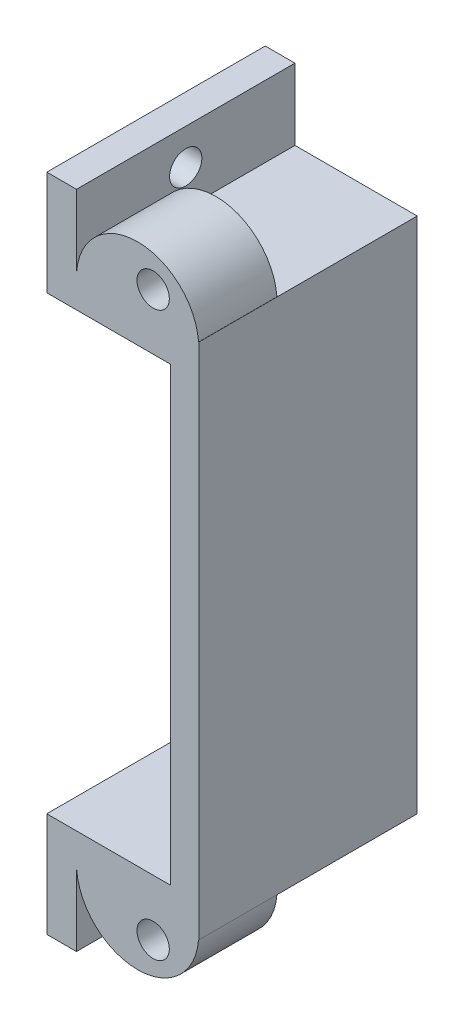
SolidWorks part; units mm, degrees
ref_plane "Front Plane" through (0, 0, 0) normal (0, 0, 1) x (1, 0, 0)
ref_plane "Top Plane" through (0, 0, 0) normal (0, 1, 0) x (1, 0, 0)
ref_plane "Right Plane" through (0, 0, 0) normal (1, 0, 0) x (0, 0, -1)
sketch "Sketch1" plane through (0, 0, 0) normal (0, 0, 1) x (1, 0, 0)
  line L0 (13, -24) -> (16, -24)
  line L1 (-13, -24) -> (13, -24) construction
  line L2 (-13, -24) -> (-13, 24) construction
  line L3 (-13, 24) -> (13, 24) construction
  line L4 (13, -24) -> (13, 24) construction
  line L5 (-13, -24) -> (13, 24) construction
  line L6 (-13, 24) -> (13, -24) construction
  line L7 (16, -24) -> (16, 27)
  line L8 (16, 27) -> (0, 27)
  line L10 (-13, 24) -> (13, 24)
  line L11 (13, 24) -> (13, -24)
  line L12 (0, 24) -> (0, 27) construction
  line L13 (3.1271, 24) -> (3.1271, 27)
  line L14 (9.5636, 24) -> (9.5636, 33.4364) construction
  line L15 (0, 27) -> (0, 34.5)
  line L16 (0, 24) -> (0, 27)
  line L17 (3.1271, 27) -> (3.1271, 34.5)
  line L18 (3.1271, 34.5) -> (0, 34.5)
  line L19 (0, -24) -> (0, -27)
  line L20 (0, -27) -> (16, -27)
  line L21 (16, -27) -> (16, -24)
  line L22 (13, -24) -> (0, -24)
  line L23 (3.1271, -24) -> (3.1271, -34.5)
  line L24 (3.1271, -34.5) -> (0, -34.5)
  line L25 (0, -34.5) -> (0, -27)
  line L26 (11.328, 27) -> (11.328, 24)
  arc A0 (3.1271, 27) -> (16, 27) centre (9.5636, 27) cw
  point P0 (0, 0)
  dimension "D1" = 26
  dimension "D2" = 48
  dimension "D3" = 3
  dimension "D4" = 3
  dimension "D5" = 7.5
  dimension "D6" = 3
  dimension "D7" = 10.5
extrude "Boss-Extrude1" add sketch "Sketch1" along normal blind 23 contours L13 L10 L11 L0 L7 L8 | L17 L18 L15 L8 | L16 L10 L13 L8 | L25 L24 L23 L20 | L23 L22 L19 L20 | L22 L23 L20 L21 L0 | A0 L8 | L26 L8 L13 L10 region at (14.4258, 2.2619, 0) region at (9.5636, -25.5, 0) region at (1.5636, -25.5, 0) region at (9.5636, 29.7317, 0) region at (7.2275, 25.5, 0) region at (1.5636, -30.75, 0) region at (1.5636, 25.5, 0) region at (1.5636, 30.75, 0)
sketch "Sketch2" plane through (3.1271, 0, 0) normal (1, 0, 0) x (0, 0, -1)
  line L0 (-23, 34.5) -> (0, 27) construction
  line L1 (0, 27) -> (0, 34.5) construction
  line L2 (0, 34.5) -> (-23, 27) construction
  line L3 (-14.75, 30.75) -> (-14.75, 34.5)
  line L4 (-23, 34.5) -> (0, 34.5) construction
  line L5 (-8.25, 30.75) -> (-8.25, 34.5)
  line L6 (-14.75, 34.5) -> (-8.25, 34.5)
  line L7 (-11.5, 27.5) -> (0, 27.5)
  line L8 (-11.5, 27.5) -> (-14.75, 27.5)
  line L9 (-14.75, 27.5) -> (-14.75, 30.75)
  circle A0 centre (-11.5, 30.75) radius 1.7
  circle A1 centre (-11.5, 30.75) radius 3.25
  point P12 (-11.5, 30.75)
  line M4 (0, 27) -> (0, 34.5)
  line M5 (0, 34.5) -> (-23, 34.5)
  dimension "D1" = 3.4
  dimension "D2" = 6.5
extrude "Cut-Extrude1" cut sketch "Sketch2" against normal through all and the other way through all contours A0
extrude "Cut-Extrude5" cut sketch "Sketch2<8>" along normal blind 23 contours A1 L5 L3 M5 | A1 A0 | A1 L9 L8 | A1 L7 L5 M4 M5 region at (3.1271, 28.2259, 14.0241) region at (3.1271, 32.625, 14.675) region at (3.1271, 33.9081, 11.5) region at (3.1271, 30.8952, 4.3082)
sketch "Sketch2<8>" plane through (3.1271, 0, 0) normal (1, 0, 0) x (0, 0, -1) same geometry as "Sketch2"
ref_plane "Plane1" through (0, 0.25, 0) normal (0, -1, 0) x (-1, 0, 0)
mirror "Mirror5" about plane through (0, 0.25, 0) normal (0, -1, 0) of "Cut-Extrude1", "Boss-Extrude1", "Cut-Extrude5"
sketch "Sketch5" plane through (0, 0, 23) normal (0, 0, 1) x (1, 0, 0)
  line L0 (15.9805, 27.5) -> (3.1271, 27.5)
  line L1 (13, 24) -> (13, 32.4423)
  arc A0 (15.9805, 27.5) -> (3.1466, 27.5) centre (9.5636, 27) ccw construction
  circle A1 centre (11.2, 29.9) radius 1.7
  dimension "D1" = 3.4
  dimension "D2" = 1.8
  dimension "D3" = 2.4
extrude "Cut-Extrude6" cut sketch "Sketch5" against normal through all contours A1 region at (11.2, 29.9, 23)
mirror "Mirror8" about plane through (0, 0.25, 0) normal (0, -1, 0) of "Cut-Extrude6"
sketch "Sketch6" plane through (3.1271, 0, 0) normal (1, 0, 0) x (0, 0, -1)
  line L0 (-23, 35) -> (0, 27.5)
  line L1 (0, 35) -> (-23, 27.5)
  circle A1 centre (-11.5, 31.25) radius 1.7
  dimension "D1" = 3.4
extrude "Cut-Extrude7" cut sketch "Sketch6" against normal blind 23 contours L1 A1 L0 | L1 A1 L0 | L0 A1 L1 | L0 A1 L1 region at (3.1271, 32.1082, 11.5) region at (3.1271, 31.25, 12.6147) region at (3.1271, 31.25, 10.3853) region at (3.1271, 30.3918, 11.5)
